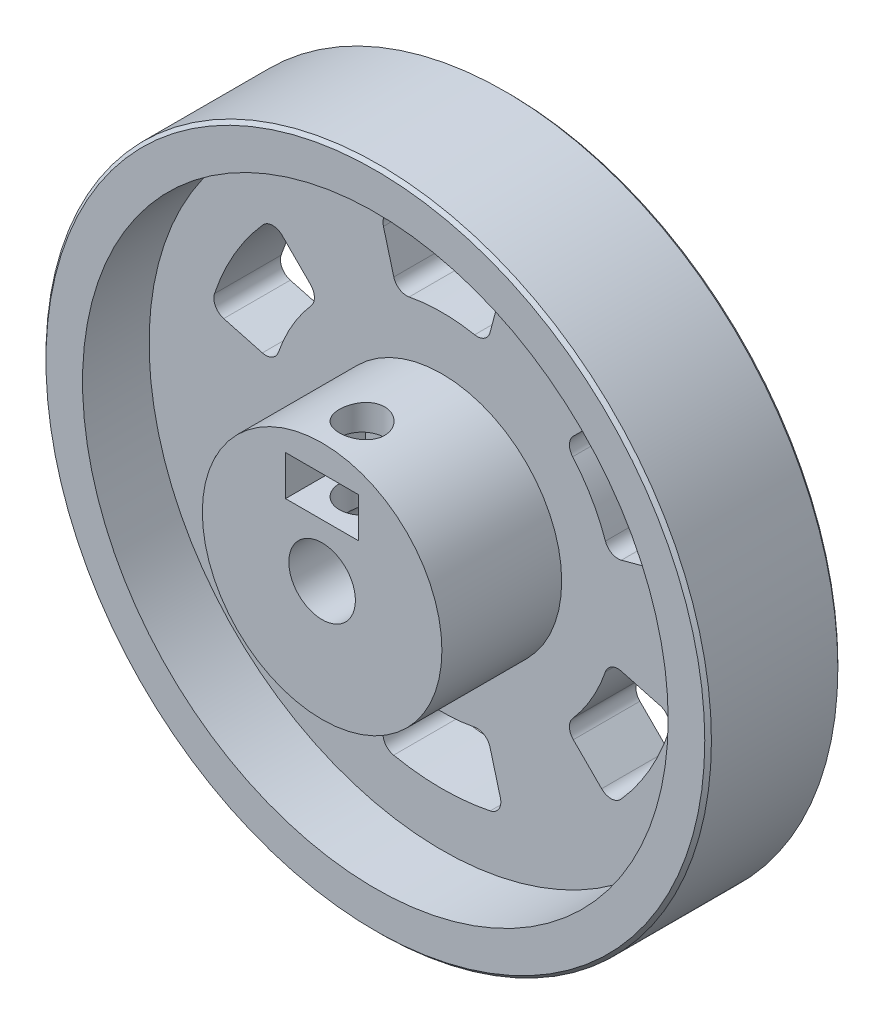
SolidWorks part; units mm, degrees
material "ABS"
ref_plane "Front Plane" through (0, 0, 0) normal (0, 0, 1) x (1, 0, 0)
ref_plane "Top Plane" through (0, 0, 0) normal (0, 1, 0) x (1, 0, 0)
ref_plane "Right Plane" through (0, 0, 0) normal (1, 0, 0) x (0, 0, -1)
sketch "Sketch1" plane through (0, 0, 0) normal (0, 0, 1) x (1, 0, 0)
  circle A0 centre (0, 0) radius 25
  dimension "D1" = 50
extrude "Boss-Extrude1" add sketch "Sketch1" along normal blind 5
sketch "Sketch3" plane through (0, 0, 0) normal (0, 0, 1) x (1, 0, 0)
  circle A0 centre (0, 0) radius 22
  circle A1 centre (0, 0) radius 25 construction
  circle A2 centre (0, 0) radius 25
  dimension "D1" = 3
extrude "Boss-Extrude3" add sketch "Sketch3" along normal blind 10
sketch "Sketch4" plane through (0, 0, 0) normal (0, 0, 1) x (1, 0, 0)
  circle A0 centre (0, 0) radius 9
  dimension "D1" = 18
extrude "Boss-Extrude4" add sketch "Sketch4" along normal blind 14
sketch "Sketch5" plane through (0, 0, 0) normal (0, 0, 1) x (1, 0, 0)
  circle A0 centre (0, 0) radius 2.5
  dimension "D1" = 5
extrude "Cut-Extrude1" cut sketch "Sketch5" along normal through all
sketch "Sketch6" plane through (0, 0, 14) normal (0, 0, 1) x (1, 0, 0)
  line L0 (0, 5.5) -> (0, 0) construction
  line L1 (-2.75, 7) -> (2.75, 7)
  line L2 (-2.75, 7) -> (-2.75, 4)
  line L3 (-2.75, 4) -> (2.75, 4)
  line L4 (2.75, 7) -> (2.75, 4)
  line L5 (-2.75, 7) -> (2.75, 4) construction
  line L6 (-2.75, 4) -> (2.75, 7) construction
  point P0 (0, 5.5)
  dimension "D1" = 3
  dimension "D2" = 5.5
  dimension "D3" = 5.5
extrude "Cut-Extrude2" cut sketch "Sketch6" against normal blind 6
sketch "Sketch7" plane through (0, 0, 0) normal (0, 1, 0) x (1, 0, 0)
  line L0 (0, 0) -> (0, -11) construction
  line L1 (2.75, -14) -> (-2.75, -14) construction
  circle A0 centre (0, -11) radius 1.7
  point P3 (0, -14)
  dimension "D2" = 3.4
  dimension "D1" = 3
extrude "Cut-Extrude3" cut sketch "Sketch7" along normal up to surface (9 mm away) up to face at (9, 0, 5)
sketch "Sketch8" plane through (0, 0, 0) normal (0, 0, 1) x (1, 0, 0)
  line L0 (0, 22) -> (0, 9) construction
  line L1 (0, 0) -> (-5.694, 21.2504) construction
  line L2 (-4.3923, 16.3923) -> (-3.6142, 13.4884)
  line L3 (0, 18) -> (0, 13) construction
  line L4 (4.3923, 16.3923) -> (3.6142, 13.4884)
  arc A0 (-3.6279, 17.6306) -> (3.6279, 17.6306) centre (0, 0) cw
  circle A1 centre (0, 0) radius 22 construction
  circle A2 centre (0, 0) radius 22 construction
  circle A3 centre (0, 0) radius 9 construction
  arc A4 (-2.4591, 12.7653) -> (2.4591, 12.7653) centre (0, 0) cw
  arc A5 (-2.4591, 12.7653) -> (-3.6142, 13.4884) centre (-2.6483, 13.7472) cw
  arc A6 (-3.6279, 17.6306) -> (-4.3923, 16.3923) centre (-3.4264, 16.6511) ccw
  arc A7 (2.4591, 12.7653) -> (3.6142, 13.4884) centre (2.6483, 13.7472) ccw
  arc A8 (3.6279, 17.6306) -> (4.3923, 16.3923) centre (3.4264, 16.6511) cw
  point P11 (0, 15.5)
  point P19 (-3.3646, 12.557)
  point P22 (-4.6587, 17.3867)
  point P23 (0, 15.5)
  dimension "D1" = 1
  dimension "D2" = 4
  dimension "D3" = 15
extrude "Cut-Extrude4" cut sketch "Sketch8" along normal through all
pattern_circular "CirPattern1" count 6 over 360 about axis through (0, 0, 14) along (0, 0, 1) of "Cut-Extrude4"
chamfer "Chamfer1" distance 0.25 angle 45 2 edges at (25, 0, 10) (25, 0, 0)
ref_plane "Plane1" through (0, 0, 5) normal (0, 0, 1) x (1, 0, 0)
